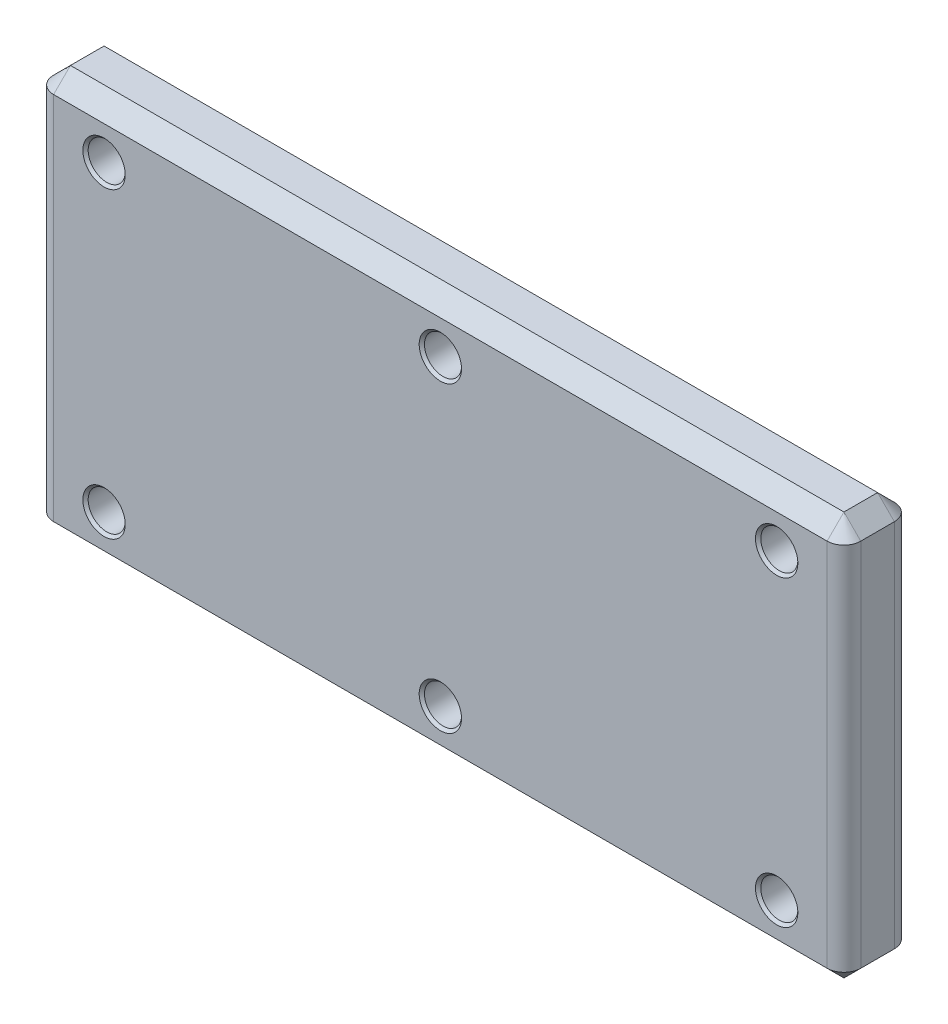
SolidWorks part; units mm, degrees
material "ABS"
ref_plane "Front Plane" through (0, 0, 0) normal (0, 0, 1) x (1, 0, 0)
ref_plane "Top Plane" through (0, 0, 0) normal (0, 1, 0) x (1, 0, 0)
ref_plane "Right Plane" through (0, 0, 0) normal (1, 0, 0) x (0, 0, -1)
ref_axis "X Axis" through (88.99, 0, 0) along (-1, 0, 0)
ref_axis "Y Axis" through (0, 55, 0) along (0, -1, 0)
ref_axis "Z Axis" through (0, 0, -88.99) along (0, 0, 1)
sketch "Sketch1" plane through (0, 0, 0) normal (0, 0, 1) x (1, 0, 0)
  line L1 (38.1, -19.05) -> (-38.1, -19.05)
  line L2 (38.1, -19.05) -> (38.1, 19.05)
  line L3 (38.1, 19.05) -> (-38.1, 19.05)
  line L4 (-38.1, -19.05) -> (-38.1, 19.05)
  line L5 (0, 19.05) -> (0, -19.05) construction
  line L6 (38.1, 0) -> (-38.1, 0) construction
  point P0 (0, 0)
  dimension "D1" = 76.2
  dimension "D2" = 38.1
extrude "Boss-Extrude1" add sketch "Sketch1" along normal mid plane 6.35
extrude "Boss-Extrude2" add sketch "Sketch1<2>" along normal mid plane 6.35
sketch "Sketch1<2>" plane through (0, 0, 0) normal (0, 0, 1) x (1, 0, 0) same geometry as "Sketch1"
sketch "Sketch8" plane through (0, 0, 0) normal (0, 1, 0) x (1, 0, 0)
  line L5 (-0.7402, 2.545) -> (-1, 2.545)
  line L6 (1, 2.545) -> (-1, 2.545) construction
  line L15 (1, 2.545) -> (1, 3.175)
  line L16 (1, 3.175) -> (-1, 3.175)
  line L19 (-1, 2.545) -> (-1, 3.175)
  line L20 (0, 3.175) -> (0, 1.795) construction
  line L21 (1, 2.799) -> (-1, 2.799) construction
  line L22 (0.7402, 2.545) -> (1, 2.545)
  line L23 (38.1, 3.175) -> (-38.1, 3.175) construction
  arc A6 (-0.5915, 2.4146) -> (-0.7402, 2.545) centre (-0.7402, 2.395) ccw
  arc A7 (-0.4989, 2.1068) -> (0.4989, 2.1068) centre (0, 2.35) ccw
  arc A8 (-0.5915, 2.4146) -> (-0.4989, 2.1068) centre (0.4, 2.545) ccw
  arc A9 (0.5915, 2.4146) -> (0.7402, 2.545) centre (0.7402, 2.395) cw
  arc A10 (0.5915, 2.4146) -> (0.4989, 2.1068) centre (-0.4, 2.545) cw
  point P0 (0, 2.799)
  dimension "D6" = 0.75
  dimension "D7" = 1.38
  dimension "D2" = 0.555
  dimension "D3" = 1
  dimension "D4" = 0.15
  dimension "D1" = 2
  dimension "D5" = 0.4
  dimension "D8" = 0.254
extrude "Cut-Extrude1" [suppressed] cut sketch "Sketch8" against normal mid plane 6.35 from offset 6.35 offset against normal yes
pattern_linear "LPattern1" [suppressed] count 20 spacing 2 along (1, 0, 0) count 20 spacing 2 along (-1, 0, 0) pattern seed only yes of bodies 104
pattern_linear "LPattern2" [suppressed] count 2 spacing 12.7 along (0, 1, 0) of bodies 105
sketch "Sketch10" plane through (0, 0, -3.175) normal (0, 0, -1) x (-1, 0, 0)
  line L0 (-38.1, -19.05) -> (-38.1, 19.05) construction
  line L1 (-38.1, 9.525) -> (38.1, 9.525)
  line L2 (-38.1, 9.525) -> (-38.1, 3.175)
  line L3 (-38.1, 3.175) -> (38.1, 3.175)
  line L4 (38.1, 9.525) -> (38.1, 3.175)
  line L5 (0, 3.175) -> (0, 9.525) construction
  line L6 (-38.1, 6.35) -> (38.1, 6.35) construction
  line L7 (38.1, 19.05) -> (38.1, -19.05) construction
  line L8 (0, 3.175) -> (0, -3.175) construction
  line L9 (-38.1, -3.175) -> (38.1, -3.175)
  line L10 (-38.1, -3.175) -> (-38.1, -9.525)
  line L11 (-38.1, -9.525) -> (38.1, -9.525)
  line L12 (38.1, -3.175) -> (38.1, -9.525)
  line L13 (0, -9.525) -> (0, -3.175) construction
  line L14 (-38.1, -6.35) -> (38.1, -6.35) construction
  point P14 (0, 0)
  point P76 (0, 6.35)
  point P81 (0, -6.35)
  dimension "D1" = 6.35
  dimension "D2" = 12.7
extrude "Cut-Extrude2" cut sketch "Sketch10" against normal blind 0.254
sketch "Sketch2" plane through (0, 0, 0) normal (0, 0, 1) x (1, 0, 0)
  line L1 (31.75, -14.2875) -> (-31.75, -14.2875) construction
  line L2 (31.75, -14.2875) -> (31.75, 14.2875) construction
  line L3 (31.75, 14.2875) -> (-31.75, 14.2875) construction
  line L4 (-31.75, -14.2875) -> (-31.75, 14.2875) construction
  line L5 (0, 14.2875) -> (0, -14.2875) construction
  line L6 (31.75, 0) -> (-31.75, 0) construction
  point P0 (0, 0)
  dimension "D1" = 63.5
  dimension "D2" = 28.575
sketch "Sketch5" plane through (0, 0, 3.175) normal (0, 0, 1) x (1, 0, 0)
  point P0 (-31.75, 14.2875)
  point P3 (-31.75, -14.2875)
  point P6 (0, 14.2875)
  point P9 (0, -14.2875)
  point P12 (31.75, 14.2875)
  point P15 (31.75, -14.2875)
hole_wizard "M3 Clearance Hole1" positions "Sketch5" profile "Sketch4" hole size "M3" standard "ANSI Metric" end condition up to next
sketch "Sketch4" plane through (-31.75, 14.2875, 3.175) normal (1, 0, 0) x (0, -1, 0)
  line L0 (0, 0) -> (0, 6.35)
  line L1 (0, 6.35) -> (2, 6.35)
  line L2 (1.75, 6.1) -> (1.75, 0.25)
  line L3 (1.75, 0.25) -> (2, 0)
  line L5 (2, 0) -> (0, 0)
  line L6 (-1.75, 0.25) -> (-2, 0) construction
  line L7 (2, 6.35) -> (1.75, 6.1)
  line L8 (-2, 6.35) -> (-1.75, 6.1) construction
  line L11 (0, -6.35) -> (0, 107.95) construction
  dimension "Thru Hole Dia." = 3.5
  dimension "Thru Hole Depth" = 6.35
  dimension "Near C'Sink Dia." = 4
  dimension "Near C'Sink Angle" = 90
  dimension "Far C'Sink Dia." = 4
  dimension "Far C'Sink Angle" = 90
fillet "Fillet1" radius 1.5875 4 edges at (-38.1, -14.2875, -3.175) (-38.1, 0, 3.175) (38.1, 0, 3.175) (38.1, -14.2875, -3.175)
chamfer "Chamfer1" distance 1.5875 angle 45 16 edges at (-38.1, 19.05, 0) (-37.635, 19.05, 2.71) (-37.635, 19.05, -2.71) (0, 19.05, 3.175) (0, 19.05, -3.175) (37.635, 19.05, 2.71) (37.635, 19.05, -2.71) (38.1, 19.05, 0) (-38.1, -19.05, 0) (-37.635, -19.05, 2.71) (-37.635, -19.05, -2.71) (0, -19.05, 3.175) (0, -19.05, -3.175) (37.635, -19.05, 2.71) (37.635, -19.05, -2.71) (38.1, -19.05, 0)
chamfer "Chamfer2" [suppressed] distance 0.254 angle 45
chamfer "Chamfer3" distance 0.254 angle 45 12 edges at (36.9615, -9.525, -3.1102) (-36.9615, -9.525, -3.1102) (0, -9.525, -3.175) (-36.9615, -3.175, -3.1102) (36.9615, -3.175, -3.1102) (0, -3.175, -3.175) (36.9615, 3.175, -3.1102) (-36.9615, 3.175, -3.1102) (0, 3.175, -3.175) (-36.9615, 9.525, -3.1102) (36.9615, 9.525, -3.1102) (0, 9.525, -3.175)
